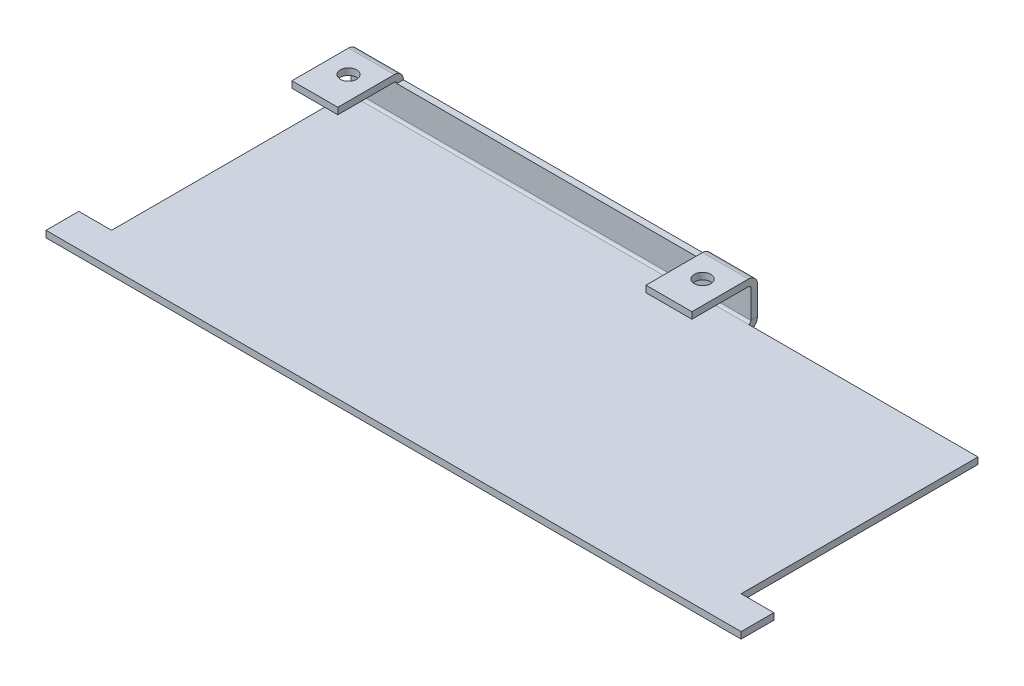
SolidWorks part; units mm, degrees
note: The reader was unsure of these and kept them because the rebuilt part matched: flange length of "Edge-Flange1", "Edge-Flange2".
material "5052-H34"
ref_plane "Front Plane" through (0, 0, 0) normal (0, 0, 1) x (1, 0, 0)
ref_plane "Top Plane" through (0, 0, 0) normal (0, 1, 0) x (1, 0, 0)
ref_plane "Right Plane" through (0, 0, 0) normal (1, 0, 0) x (0, 0, -1)
sketch "Sketch1" plane through (0, 0, 0) normal (0, 1, 0) x (1, 0, 0)
  line L1 (0, 0) -> (212, 0)
  line L2 (0, 0) -> (0, 85)
  line L3 (0, 85) -> (212, 85)
  line L4 (212, 0) -> (212, 85)
  dimension "D1" = 212
  dimension "D2" = 85
base flange "Base-Flange1" sketch "Sketch1" thickness 2 reverse thickness direction no parameters "D1"=0.7366
sketch "Sketch6" plane through (0, 0, 0) normal (0, 1, 0) x (1, 0, 0)
  line L0 (0, 0) -> (212, 0) construction
  line L1 (0, 85) -> (10, 85)
  line L2 (0, 85) -> (0, 10)
  line L3 (0, 10) -> (10, 10)
  line L4 (10, 85) -> (10, 10)
  line L5 (212, 85) -> (202, 85)
  line L6 (212, 85) -> (212, 10)
  line L7 (212, 10) -> (202, 10)
  line L8 (202, 85) -> (202, 10)
  dimension "D1" = 10
  dimension "D2" = 10
  dimension "D3" = 10
extrude "Cut-Extrude1" cut sketch "Sketch6" against normal up to next normal cut yes
edge flange "Edge-Flange1" sketch "Sketch9" flange angle 90 flange length 12 flange position material inside bend radius 0.7366 thickness 2 relief rectangular parameters "D6"=10
sketch "Sketch9" plane through (0, 0, -85) normal (0, 0, -1) x (-1, 0, 0)
  line L0 (-202, 0) -> (-10, 0) construction
  line L1 (-202, 0) -> (-10, 0)
  line L2 (-202, 0) -> (-202, 10)
  line L3 (-202, 10) -> (-10, 10)
  line L4 (-10, 10) -> (-10, 0)
bend "EdgeBend1" bend radius 0.7366 bend angle 90 parameters "D5"=1
edge flange "Edge-Flange2" sketch "Sketch12" flange angle 90 flange length 20 flange position material outside bend radius 0.7366 thickness 2 relief rectangular parameters "D6"=10
sketch "Sketch12" plane through (0, 10, -83) normal (0, 1, 0) x (-1, 0, 0)
  line L2 (-202, 0) -> (-202, 18)
  line L3 (-202, 18) -> (-10, 18)
  line L4 (-10, 18) -> (-10, 0)
  line L5 (-10, 0) -> (-202, 0) construction
  line L6 (-10, 0) -> (-202, 0)
bend "EdgeBend2" bend radius 0.7366 bend angle 90 parameters "D5"=2
sketch "Sketch13" plane through (0, 12, 0) normal (0, 1, 0) x (1, 0, 0)
  line L0 (10, 82.2634) -> (202, 82.2634) construction
  line L3 (10, 82.2634) -> (10, 65) construction
  line L4 (10, 85) -> (202, 85) construction
  line L5 (10, 65) -> (202, 65) construction
  line L6 (202, 65) -> (132, 65)
  line L7 (202, 65) -> (202, 85)
  line L8 (202, 85) -> (132, 85)
  line L9 (132, 65) -> (132, 85)
  line L10 (118, 85) -> (24, 85)
  line L11 (118, 85) -> (118, 65)
  line L12 (118, 65) -> (24, 65)
  line L13 (24, 85) -> (24, 65)
  line L14 (10, 75.2634) -> (202, 75.2634) construction
  line L15 (17, 65) -> (17, 85) construction
  line L16 (125, 65) -> (125, 85) construction
  circle A0 centre (125, 75.2634) radius 2.5
  circle A1 centre (17, 75.2634) radius 2.5
  dimension "D2" = 5
  dimension "D1" = 108
  dimension "D3" = 14
  dimension "D4" = 7
  dimension "D5" = 14
  dimension "D6" = 7
  dimension "D7" = 7
extrude "Cut-Extrude2" cut sketch "Sketch13" against normal up to vertex
sketch "Sketch14" plane through (0, 0, -85) normal (0, 0, -1) x (-1, 0, 0)
  line L2 (-202, 9.2634) -> (-132, 9.2634)
  line L3 (-202, 9.2634) -> (-202, -2)
  line L4 (-202, -2) -> (-132, -2)
  line L6 (-132, 9.2634) -> (-132, -2)
  line L7 (-10, -2) -> (-202, -2) construction
extrude "Cut-Extrude3" cut sketch "Sketch14" against normal up to vertex
sketch "Bend-Lines1" plane through (0, 0, 0) normal (0, 1, 0) x (1, 0, 0)
sketch "Bounding-Box1" plane through (0, 0, 0) normal (0, 1, 0) x (1, 0, 0)
sheet metal parameters "Sheet-Metal1" thickness 2 parameters "D1"=0.7366
flat pattern "Flat-Pattern1" [suppressed]
sketch "Bend-Lines2" plane through (0, 0, 0) normal (0, 1, 0) x (1, 0, 0)
sketch "Bounding-Box2" [suppressed] plane through (0, 0, 0) normal (0, 1, 0) x (1, 0, 0)
sheet metal parameters "Sheet-Metal2" thickness 2 parameters "D1"=0.7366
flat pattern "Flat-Pattern1"
sketch "Bend-Lines2" plane through (0, 0, 0) normal (0, 1, 0) x (1, 0, 0)
sketch "Bounding-Box2" [suppressed] plane through (0, 0, 0) normal (0, 1, 0) x (1, 0, 0)
sheet metal parameters "Sheet-Metal3" thickness 2 parameters "D1"=0.7366
flat pattern "Flat-Pattern1" [suppressed]
sketch "Bend-Lines2" plane through (0, 0, 0) normal (0, 1, 0) x (1, 0, 0)
sketch "Bounding-Box2" [suppressed] plane through (0, 0, 0) normal (0, 1, 0) x (1, 0, 0)
bend of the flat pattern "Flatten-<EdgeBend1>1"
sheet metal parameters "Sheet-Metal4" thickness 2 parameters "D1"=0.7366
flat pattern "Flat-Pattern1" [suppressed]
sketch "Bend-Lines2" plane through (0, 0, 0) normal (0, 1, 0) x (1, 0, 0)
sketch "Bounding-Box2" [suppressed] plane through (0, 0, 0) normal (0, 1, 0) x (1, 0, 0)
bend of the flat pattern "Flatten-<EdgeBend1>1"
bend of the flat pattern "Flatten-<EdgeBend2>1"
sheet metal parameters "Sheet-Metal5" thickness 2 parameters "D1"=0.7366
flat pattern "Flat-Pattern1" [suppressed]
sketch "Bend-Lines2" plane through (0, 0, 0) normal (0, 1, 0) x (1, 0, 0)
sketch "Bounding-Box2" [suppressed] plane through (0, 0, 0) normal (0, 1, 0) x (1, 0, 0)
bend of the flat pattern "Flatten-<EdgeBend1>1"
bend of the flat pattern "Flatten-<EdgeBend2>1"
sheet metal parameters "Sheet-Metal6" thickness 2 parameters "D1"=0.7366
flat pattern "Flat-Pattern1" [suppressed]
sketch "Bend-Lines2" plane through (0, 0, 0) normal (0, 1, 0) x (1, 0, 0)
sketch "Bounding-Box2" [suppressed] plane through (0, 0, 0) normal (0, 1, 0) x (1, 0, 0)
bend of the flat pattern "Flatten-<EdgeBend1>1"
bend of the flat pattern "Flatten-<EdgeBend2>1"
